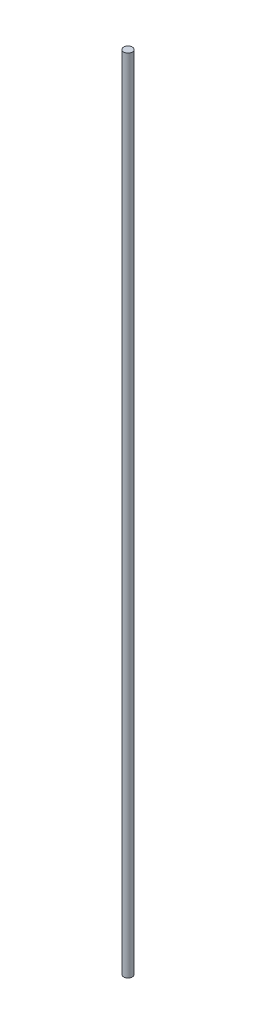
SolidWorks part; units mm, degrees
ref_plane "Front Plane" through (0, 0, 0) normal (0, 0, 1) x (1, 0, 0)
ref_plane "Top Plane" through (0, 0, 0) normal (0, 1, 0) x (1, 0, 0)
ref_plane "Right Plane" through (0, 0, 0) normal (1, 0, 0) x (0, 0, -1)
sketch "Sketch1" plane through (0, 0, 0) normal (0, 1, 0) x (1, 0, 0)
  circle A0 centre (0, 0) radius 5.08
extrude "Boss-Extrude1" add sketch "Sketch1" along normal blind 932.688
